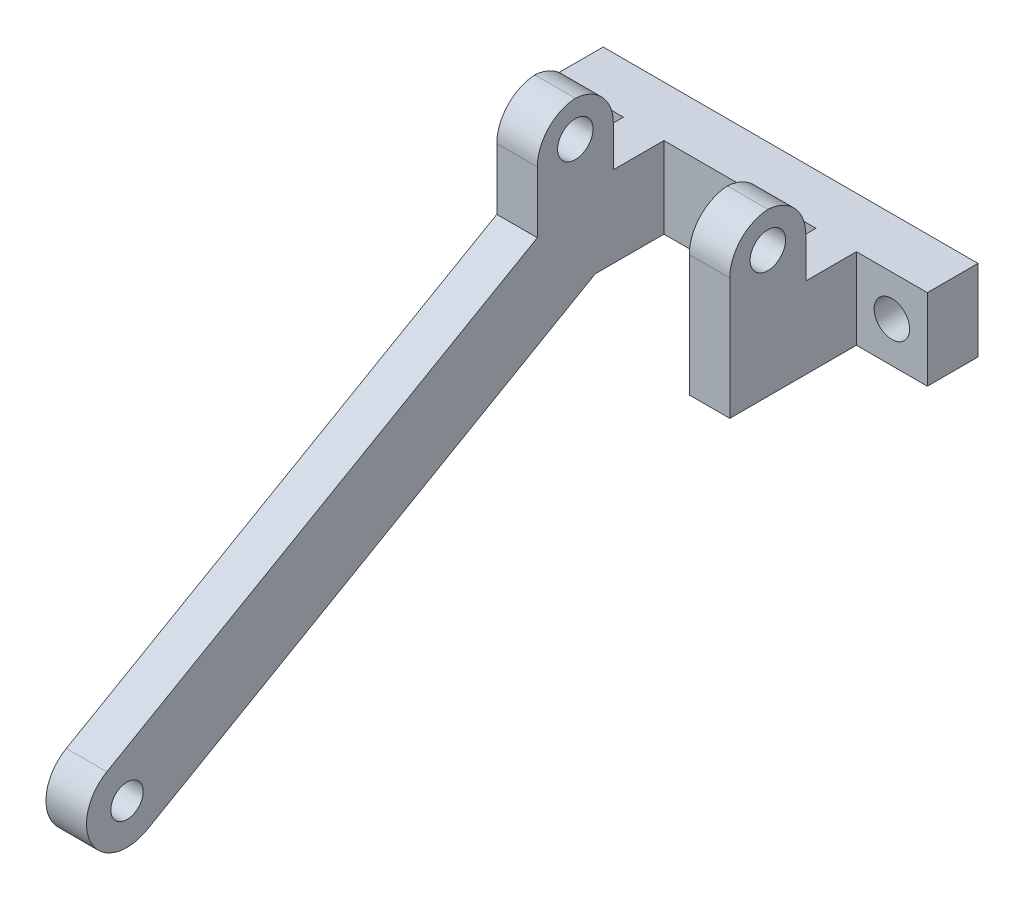
SolidWorks part; units mm, degrees
ref_plane "Front Plane" through (0, 0, 0) normal (0, 0, 1) x (1, 0, 0)
ref_plane "Top Plane" through (0, 0, 0) normal (0, 1, 0) x (1, 0, 0)
ref_plane "Right Plane" through (0, 0, 0) normal (1, 0, 0) x (0, 0, -1)
sketch "Sketch1" plane through (0, 0, 0) normal (0, 0, 1) x (1, 0, 0)
  line L0 (15, 0) -> (-15, 0) construction
  line L1 (-18.5, 4) -> (18.5, 4)
  line L2 (-18.5, 4) -> (-18.5, -4)
  line L3 (-18.5, -4) -> (18.5, -4)
  line L4 (18.5, 4) -> (18.5, -4)
  line L5 (-18.5, 4) -> (18.5, -4) construction
  line L6 (-18.5, -4) -> (18.5, 4) construction
  line L7 (0, -4) -> (0, 4) construction
  circle A0 centre (-15, 0) radius 1.75
  circle A1 centre (15, 0) radius 1.75
  point P0 (0, 0)
  point P12 (0, 0)
  dimension "D3" = 3.5
  dimension "D1" = 37
  dimension "D2" = 8
  dimension "D4" = 15
extrude "Boss-Extrude1" add sketch "Sketch1" along normal blind 5
sketch "Sketch2" plane through (0, 0, 5) normal (0, 0, 1) x (1, 0, 0)
  line L0 (0, 4) -> (0, -4) construction
  line L1 (18.5, 4) -> (-18.5, 4) construction
  line L2 (-18.5, -4) -> (18.5, -4) construction
  line L3 (11.5, -4) -> (7.5, 4) construction
  line L4 (-11.5, 4) -> (-7.5, 4)
  line L5 (-11.5, 4) -> (-11.5, -4)
  line L6 (-11.5, -4) -> (-7.5, -4)
  line L7 (-7.5, 4) -> (-7.5, -4)
  line L8 (-11.5, 4) -> (-7.5, -4) construction
  line L9 (-11.5, -4) -> (-7.5, 4) construction
  line L10 (11.5, 4) -> (7.5, -4) construction
  line L11 (7.5, 4) -> (7.5, -4)
  line L12 (11.5, -4) -> (7.5, -4)
  line L13 (11.5, 4) -> (11.5, -4)
  line L14 (11.5, 4) -> (7.5, 4)
  point P6 (-9.5, 0)
  point P15 (9.5, 0)
  dimension "D1" = 7.5
  dimension "D2" = 4
extrude "Boss-Extrude2" add sketch "Sketch2" along normal blind 12.5
sketch "Sketch4" plane through (0, 4, 0) normal (0, 1, 0) x (1, 0, 0)
  line L0 (-7.5, -17.5) -> (-7.5, -5) construction
  line L1 (-11.5, -17.5) -> (-7.5, -17.5)
  line L2 (-11.5, -17.5) -> (-11.5, -10)
  line L3 (-11.5, -10) -> (-7.5, -10)
  line L4 (-7.5, -17.5) -> (-7.5, -10)
  line L5 (0, 0) -> (0, -5) construction
  line L6 (7.5, -5) -> (-7.5, -5) construction
  line L7 (7.5, -17.5) -> (7.5, -10)
  line L8 (11.5, -10) -> (7.5, -10)
  line L9 (11.5, -17.5) -> (11.5, -10)
  line L10 (11.5, -17.5) -> (7.5, -17.5)
  dimension "D1" = 7.5
extrude "Boss-Extrude3" add sketch "Sketch4" along normal blind 8
sketch "Sketch3" plane through (-11.5, 0, 0) normal (-1, 0, 0) x (0, 0, 1)
  line L0 (10, 8.5) -> (17.5, 8.5) construction
  line L4 (10, 12) -> (10, 4) construction
  line L5 (17.5, 12) -> (17.5, -4) construction
  line L6 (13.75, 8.5) -> (13.75, 12) construction
  line L7 (10, 12) -> (17.5, 12) construction
  circle A0 centre (13.75, 8.5) radius 1.75
  dimension "D1" = 3.5
  dimension "D2" = 8.5
extrude "Cut-Extrude1" cut sketch "Sketch3" against normal through all
fillet "Fillet1" radius 4 4 edges at (-9.5, 12, 10) (9.5, 12, 10) (9.5, 12, 17.5) (-9.5, 12, 17.5)
sketch "Sketch5" plane through (-7.5, 0, 0) normal (1, 0, 0) x (0, 0, -1)
  line L0 (-10, 8) -> (-10, 4) construction
  line L1 (-10, 6.5) -> (-13, 6.5)
  line L2 (-10, 6.5) -> (-10, 1.5)
  line L3 (-10, 1.5) -> (-13, 1.5)
  line L4 (-13, 6.5) -> (-13, 1.5)
  line L5 (-10, 4) -> (-5, 4) construction
  dimension "D1" = 3
  dimension "D2" = 5
  dimension "D3" = 2.5
extrude "Boss-Extrude4" [suppressed] add sketch "Sketch5" along normal up to next
sketch "Sketch6" plane through (-11.5, 0, 0) normal (-1, 0, 0) x (0, 0, 1)
  line L0 (56.0113, -29.4012) -> (11.7824, -4)
  line L1 (17.5, -4) -> (5, -4) construction
  line L2 (11.7824, -4) -> (17.5, 1.9418)
  line L3 (13.75, 8.5) -> (58.0033, -25.9326) construction
  line L4 (17.5, 1.9418) -> (59.9954, -22.4639)
  line L5 (59.9954, -22.4639) -> (56.0113, -29.4012) construction
  line L6 (13.75, 8.5) -> (13.75, -4) construction
  line L7 (17.5, 8) -> (17.5, -4) construction
  circle A0 centre (58.0033, -25.9326) radius 1.6
  arc A1 (56.0113, -29.4012) -> (59.9954, -22.4639) centre (58.0033, -25.9326) ccw
  dimension "D1" = 3.2
  dimension "D2" = 8
  dimension "D3" = 52.114
  dimension "D4" = 56.071
  dimension "D5" = 1.9676
extrude "Boss-Extrude5" add sketch "Sketch6" against normal up to surface (4 mm away) up to face at (-7.5, 6.75, 13.75)
equation "\"X-ROD-SPACING\"=45"
equation "\"Y-ROD-SPACING\"=75"
equation "\"Z-ROD-SPACING\"=17.5"
equation "\"Y-BED-OFFSET\"=2"
equation "\"Y-BED-ROD-INSET\"=3.5"
equation "\"Y-BED-SCREW-SPACING\"=209"
equation "\"Y-BED-SCREW-CUTOUT-SLOT-HEIGHT\"=2"
equation "\"T-SLOT-NUT-FILLET-RADIUS\"=0.25"
equation "\"T-SLOT-SCREW-SHAFT-RADIUS\"=1.75"
equation "\"T-SLOT-SCREW-SHAFT-CUTOUT-LENGTH\"=10.5"
equation "\"T-SLOT-NUT-DEPTH\"=4.2"
equation "\"T-SLOT-NUT-WIDTH\"=3"
equation "\"T-SLOT-NUT-END-DISTANCE\"=8"
equation "\"ACRYLIC-THICKNESS\"=10"
equation "\"ACRYLIC-THICKNESS2\"=4.5"
equation "\"ACRYLIC-TAB-CUTOUT-SIZE\"=\"ACRYLIC-THICKNESS\"+\"ACRYLIC-TAB-TOLERANCE\"*2"
equation "\"ACRYLIC-TAB-TOLERANCE\"=.1"
equation "\"ACRYLIC-TAB-WIDTH\"=\"ACRYLIC-THICKNESS\""
equation "\"ACRYLIC-M3-HOLE\"=3.1"
equation "\"SMOOTHROD-CAP-SCREW-DISTANCE\"=20"
equation "\"FRAME-WIDTH-INNER\"=370"
equation "\"NEMA17-HOLE-SPACING\"=31"
equation "\"NEMA17-CENTRAL-CUTOUT\"=22.5"
equation "\"Z-BRACKET-REACH\"=55"
equation "\"Z-ROD-INSET\"=16"
equation "\"TOP-BRACKET-SPACING\"=40"
equation "\"SMOOTHROD-X-LENGTH\"=350"
equation "\"SMOOTHROD-Y-LENGTH\"=350"
equation "\"SMOOTHROD-Z-LENGTH\"=350"
equation "\"SMOOTHROD-TIGHTENING-HEADROOM\"=.25"
equation "\"LEADSCREW-Z-LENGTH\"=300"
equation "\"SCREW-LENGTH-FRAME\"=\"ACRYLIC-THICKNESS\" + 10"
equation "\"SCREW-LENGTH-MOTOR\"=\"ACRYLIC-THICKNESS\" + 5"
equation "\"SCREW-LENGTH-EXTRUDER\"=28"
equation "\"SCREW-HEAD-RADIUS\"=6"
equation "\"PRINTED-X-SMOOTHROD-DIAMETER\"=8.2"
equation "\"PRINTED-X-SMOOTHROD-CUTOUT\"=10"
equation "\"PRINTED-X-BASE-HEIGHT\"=10"
equation "\"PRINTED-LM8UU-CUTOUT-SIZE\"=15.25"
equation "\"PRINTED-LM8UU-CUTOUT-LENGTH\"=24.5"
equation "\"PRINTED-X-IDLER-HEIGHT\"=16"
equation "\"PSU-MOUNTING-WIDTH\"=95"
equation "\"PSU-MOUNTING-HEIGHT\"=177"
equation "\"Y-BELT-TO-ROD-DISTANCE\"=20"
equation "\"SPOOL-HOLDER-ROD-SPACING\"=150"
equation "\"ACRYLIC-X-CARRIAGE-WIDTH\"=55"
equation "\"ACRYLIC-X-CARRIAGE-HEIGHT\"=75"
equation "\"ACRYLIC-X-CARRIAGE-LM8UU-CUTOUT-WIDTH\"=24.25"
equation "\"ACRYLIC-X-CARRIAGE-LM8UU-CUTOUT-HEIGHT\"=11.5"
equation "\"ACRYLIC-X-CARRIAGE-SCREW-SPACING-X\"=15"
equation "\"ACRYLIC-X-CARRIAGE-SCREW-SPACING-Y\"=33"
equation "\"ACRYLIC-X-CARRIAGE-CENTER-TAB-SPACING\"=14"
equation "\"ACRYLIC-X-CARRIAGE-EXTRUDER-OFFSET\"=26"
equation "\"ACRYLIC-X-CARRIAGE-EXTRUDER-ANGLE\"=90"
equation "\"ACRYLIC-X-CARRIAGE-EXTRUDER-SHELF-DEPTH\"=\"ACRYLIC-X-CARRIAGE-EXTRUDER-OFFSET\" + 28"
equation "\"ACRYLIC-X-CARRIAGE-EXTRUDER-BRACE-SPACING\"=23"
equation "\"ACRYLIC-X-CARRIAGE-EXTRUDER-BRACE-TAB-OFFSET\"=20"
equation "\"ACRYLIC-X-CARRIAGE-EXTRUDER-BRACE-HEIGHT\"=35"
equation "\"ACRYLIC-X-CARRIAGE-EXTRUDER-BRACE-SCREW-SPACING\"=22"
equation "\"ACRYLIC-X-CARRIAGE-DUAL-WIDTH-MULTIPLIER\"=1.65"
equation "\"ACRYLIC-X-CARRIAGE-DUAL-HOTEND-SPACING\"=42"
equation "\"ACRYLIC-X-CARRIAGE-DUAL-WIDTH\"=75"
equation "\"ACRYLIC-X-CARRIAGE-DUAL-HOTEND-SEPARATION\"=36"
equation "\"ACRYLIC-X-CARRIAGE-DUAL-MOUNT-PLATE-DEPTH\"=75"
equation "\"ACRYLIC-X-CARRIAGE-DUAL-MOUNT-BRACE-WIDTH\"=33"
equation "\"ACRYLIC-X-CARRIAGE-DUAL-MOUNT-SCREW-WIDTH\"=40"
equation "\"D3@Sketch1\"=3.5"
equation "\"PRINTED-M3-HOLE\"=3.5"
equation "\"BLOWER-FAN-WIDTH\"=15"
equation "\"D1@Sketch2\"=\"BLOWER-FAN-WIDTH\"/2"
